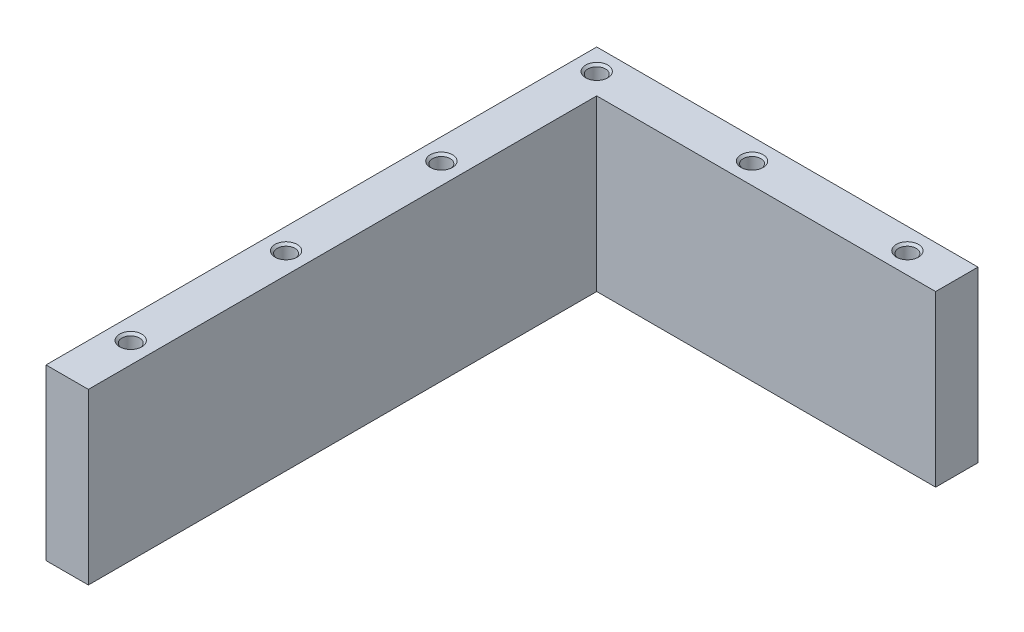
SolidWorks part; units mm, degrees
material "ABS"
ref_plane "Front Plane" through (0, 0, 0) normal (0, 0, 1) x (1, 0, 0)
ref_plane "Top Plane" through (0, 0, 0) normal (0, 1, 0) x (1, 0, 0)
ref_plane "Right Plane" through (0, 0, 0) normal (1, 0, 0) x (0, 0, -1)
sketch "Sketch1" plane through (0, 0, 0) normal (0, 1, 0) x (1, 0, 0)
  line L0 (0, 0) -> (85.725, 0)
  line L1 (85.725, 0) -> (85.725, -9.525)
  line L2 (85.725, -9.525) -> (9.525, -9.525)
  line L3 (9.525, -9.525) -> (9.525, -123.825)
  line L4 (9.525, -123.825) -> (0, -123.825)
  line L5 (0, -123.825) -> (0, 0)
  dimension "D1" = 9.525
  dimension "D2" = 9.525
  dimension "D3" = 114.3
  dimension "D4" = 76.2
extrude "Boss-Extrude1" add sketch "Sketch1" along normal blind 38.1
hole_wizard "CBORE for #4 Socket Head Cap Screw1" positions "Sketch3" profile "Sketch2" counterbore size "#4" standard "ANSI Inch"
sketch "Sketch3" plane through (0, 0, 0) normal (0, -1, 0) x (-1, 0, 0)
  line L0 (-4.7625, -123.825) -> (-4.7625, 0) construction
  line L1 (0, -123.825) -> (-9.525, -123.825) construction
  line L2 (-85.725, 0) -> (0, 0) construction
  line L4 (-85.725, -4.7625) -> (0, -4.7625) construction
  line L5 (-85.725, -9.525) -> (-85.725, 0) construction
  line L6 (0, 0) -> (0, -123.825) construction
  point P15 (-4.7625, -4.7625)
  point P17 (-4.7625, -39.6875)
  point P19 (-4.7625, -74.6125)
  point P23 (-39.6875, -4.7625)
  point P25 (-74.6125, -4.7625)
  point P27 (-4.7625, -109.5375)
  dimension "D1" = 34.925
  dimension "D2" = 34.925
  dimension "D3" = 34.925
  dimension "D4" = 34.925
  dimension "D5" = 34.925
sketch "Sketch2" plane through (4.7625, 0, 4.7625) normal (1, 0, 0) x (0, 0, -1)
  line L0 (0, 0) -> (0, 13.6806)
  line L1 (0, 13.6806) -> (1.6319, 12.7)
  line L2 (1.6319, 12.7) -> (1.6319, 4.7625)
  line L3 (1.6319, 4.7625) -> (1.9844, 4.7625)
  line L4 (1.9844, 4.7625) -> (1.9844, 0)
  line L5 (1.9844, 0) -> (0, 0)
  line L10 (0, 13.6806) -> (-1.632, 12.7) construction
  line L11 (0, -6.35) -> (0, 107.95) construction
  dimension "Hole Dia." = 3.2639
  dimension "Hole Depth" = 12.7
  dimension "C'Bore Dia." = 3.9688
  dimension "C'Bore Depth" = 4.7625
  dimension "Drill Angle" = 118
ref_plane "Mirror Plane" through (0, 19.05, 0) normal (0, 1, 0) x (1, 0, 0)
mirror "Mirror CBORE for #4 Socket Head Cap Screw" about plane through (0, 19.05, 0) normal (0, 1, 0) of "CBORE for #4 Socket Head Cap Screw1"
chamfer "Chamfer1" distance 0.508 angle 45 15 edges at (4.7625, 0, 2.7781) (4.7625, 4.7625, 2.7781) (4.7625, 0, 72.6281) (4.7625, 4.7625, 72.6281) (74.6125, 0, 2.7781) (39.6875, 0, 2.7781) (4.7625, 0, 37.7031) (4.7625, 0, 107.5531) (39.6875, 38.1, 6.7469) (39.6875, 33.3375, 6.7469) (74.6125, 38.1, 6.7469) (4.7625, 38.1, 6.7469) (4.7625, 38.1, 41.6719) (4.7625, 38.1, 76.5969) (4.7625, 38.1, 111.5219)
